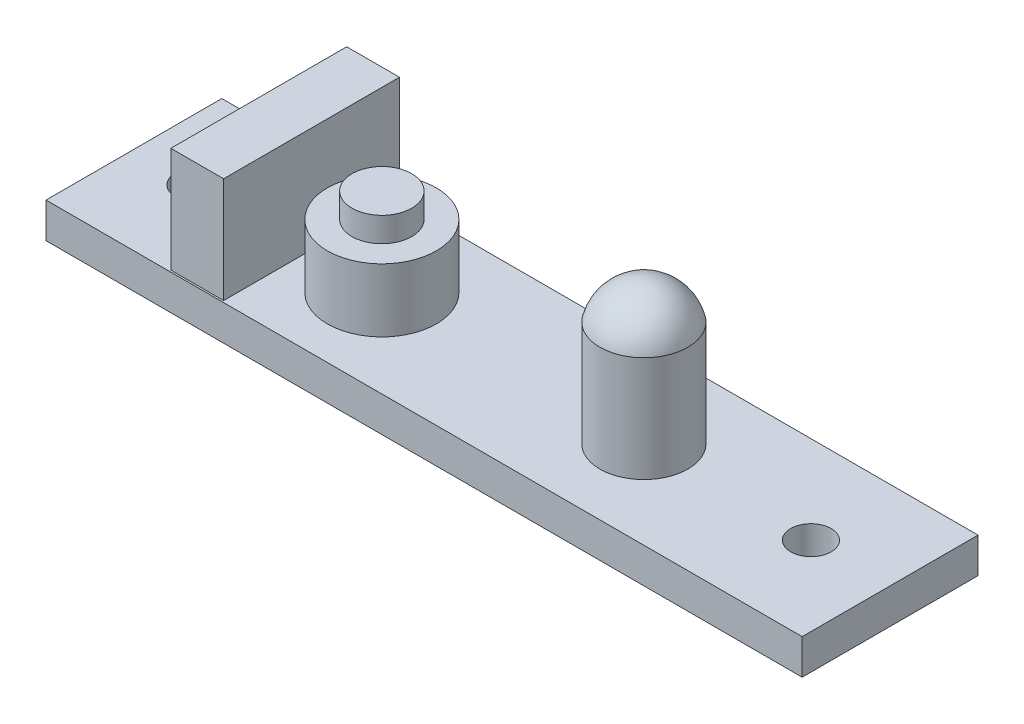
SolidWorks part; units mm, degrees
ref_plane "Front Plane" through (0, 0, 0) normal (0, 0, 1) x (1, 0, 0)
ref_plane "Top Plane" through (0, 0, 0) normal (0, 1, 0) x (1, 0, 0)
ref_plane "Right Plane" through (0, 0, 0) normal (1, 0, 0) x (0, 0, -1)
sketch "Sketch1" plane through (0, 0, 0) normal (0, 1, 0) x (1, 0, 0)
  line L1 (-21.5, 5) -> (21.5, 5)
  line L2 (-21.5, 5) -> (-21.5, -5)
  line L3 (-21.5, -5) -> (21.5, -5)
  line L4 (21.5, 5) -> (21.5, -5)
  line L5 (-21.5, 5) -> (21.5, -5) construction
  line L6 (-21.5, -5) -> (21.5, 5) construction
  point P0 (0, 0)
  dimension "D1" = 10
  dimension "D2" = 43
extrude "Boss-Extrude1" add sketch "Sketch1" along normal blind 2
sketch "Sketch2" plane through (0, 2, 0) normal (0, 1, 0) x (1, 0, 0)
  line L0 (21.5, 5) -> (-21.5, 5) construction
  line L1 (-14.5, -4.9) -> (-11.5, -4.9)
  line L2 (-14.5, -4.9) -> (-14.5, 5.1)
  line L3 (-14.5, 5.1) -> (-11.5, 5.1)
  line L4 (-11.5, -4.9) -> (-11.5, 5.1)
  line L5 (-21.5, -5) -> (21.5, -5) construction
  line L6 (-21.5, 5) -> (-21.5, -5) construction
  dimension "D1" = 0.1
  dimension "D2" = 0.1
  dimension "D3" = 7
  dimension "D4" = 3
extrude "Boss-Extrude2" add sketch "Sketch2" along normal blind 6
sketch "Sketch4" plane through (0, 2, 0) normal (0, 1, 0) x (1, 0, 0)
  line L0 (-21.5, -5) -> (21.5, -5) construction
  line L1 (-11.5, -4.9) -> (-11.5, 5) construction
  circle A0 centre (-7.4, 0) radius 3.1
  dimension "D1" = 6.2
  dimension "D2" = 5
  dimension "D3" = 4.1
extrude "Boss-Extrude3" add sketch "Sketch4" along normal blind 3.6
sketch "Sketch6" plane through (0, 5.6, 0) normal (0, 1, 0) x (1, 0, 0)
  circle A0 centre (-7.4, 0) radius 1.7
  dimension "D1" = 3.4
extrude "Boss-Extrude5" add sketch "Sketch6" along normal blind 1.4
sketch "Sketch7" plane through (0, 2, 0) normal (0, 1, 0) x (1, 0, 0)
  line L0 (21.5, -5) -> (21.5, 5) construction
  line L1 (-21.5, -5) -> (21.5, -5) construction
  circle A0 centre (7.5, 0) radius 2.5
  dimension "D1" = 5
  dimension "D2" = 14
  dimension "D3" = 5
extrude "Boss-Extrude6" add sketch "Sketch7" along normal blind 6
dome "Dome1" faces to dome 1 distance 2 reverse direction no elliptical dome no face at (7.5, 8, 2.5) parameters "D1"=2
sketch "Sketch8" plane through (0, 2, 0) normal (0, 1, 0) x (1, 0, 0)
  line L0 (-21.5, 5) -> (-21.5, -5) construction
  line L1 (-21.5, -5) -> (21.5, -5) construction
  line L2 (21.5, -5) -> (21.5, 5) construction
  line L3 (-14.5, 5) -> (-14.5, -4.9) construction
  circle A0 centre (-18, 0) radius 1.15
  circle A1 centre (17, 0) radius 1.15
  circle A2 centre (-7.4, 0) radius 1.7 construction
  circle A3 centre (7.5, 0) radius 2.5 construction
  dimension "D1" = 2.3
  dimension "D2" = 3.5
  dimension "D3" = 5
  dimension "D4" = 4.5
  dimension "D5" = 5
  dimension "D6" = 2.3
  dimension "D7" = 35
  dimension "D8" = 10.6
  dimension "D9" = 3.5
  dimension "D10" = 9.5
extrude "Cut-Extrude1" cut sketch "Sketch8" against normal through all and the other way through all
